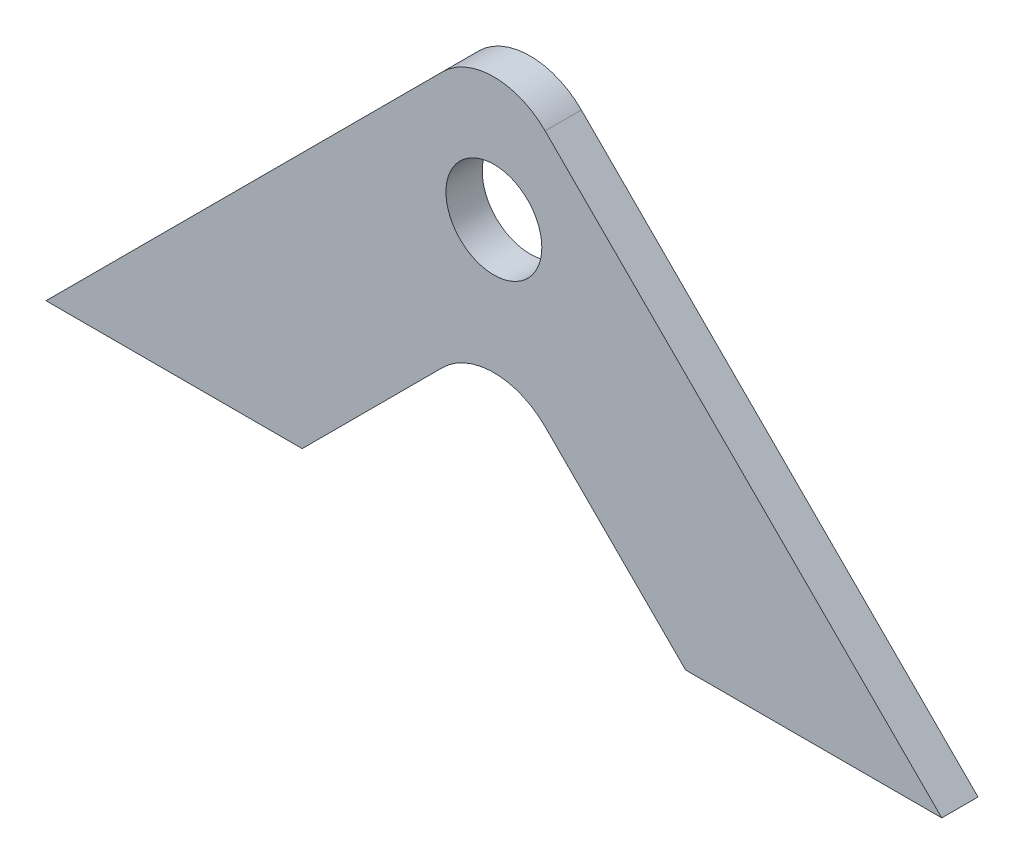
SolidWorks part; units mm, degrees
ref_plane "Front Plane" through (0, 0, 0) normal (0, 0, 1) x (1, 0, 0)
ref_plane "Top Plane" through (0, 0, 0) normal (0, 1, 0) x (1, 0, 0)
ref_plane "Right Plane" through (0, 0, 0) normal (1, 0, 0) x (0, 0, -1)
sketch "Sketch1" plane through (0, 0, 0) normal (0, 0, 1) x (1, 0, 0)
  line L3 (0, 0) -> (38.1, 38.0993) construction
  line L4 (0, 0) -> (76.2, 0) construction
  line L5 (38.1, 38.0993) -> (76.2, 0) construction
  line L6 (-13.4705, 0) -> (33.6099, 47.0795)
  line L7 (42.5901, 47.0795) -> (89.6705, 0)
  line L8 (89.6705, 0) -> (-13.4705, 0)
  line L9 (8.9803, 0) -> (33.6099, 24.6291)
  line L10 (42.5901, 24.6291) -> (67.2197, 0)
  line L11 (-1.1513, 12.319) -> (77.3513, 12.319)
  circle A0 centre (38.1, 38.0993) radius 4.1999
  arc A1 (33.6099, 24.6291) -> (42.5901, 24.6291) centre (38.1, 20.1389) cw
  arc A2 (42.5901, 47.0795) -> (33.6099, 47.0795) centre (38.1, 42.5894) ccw
  point P6 (38.1, 0)
  dimension "D3" = 8.3998
  dimension "D4" = 9.525
  dimension "D7" = 6.35
  dimension "D1" = 53.881
  dimension "D2" = 76.2
  dimension "D5" = 6.35
  dimension "D6" = 6.35
  dimension "D8" = 12.319
extrude "Boss-Extrude2" add sketch "Sketch1" along normal blind 3.175 contours L7 A2 L6 L11 A1 A0 region at (16.8418, 29.0867, 0)
